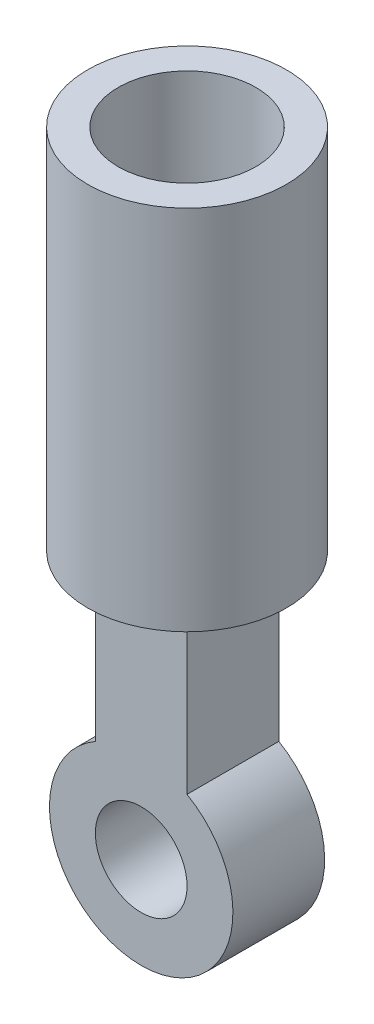
SolidWorks part; units mm, degrees
ref_plane "Front" through (0, 0, 0) normal (0, 0, 1) x (1, 0, 0)
ref_plane "Top" through (0, 0, 0) normal (0, 1, 0) x (1, 0, 0)
ref_plane "Right" through (0, 0, 0) normal (1, 0, 0) x (0, 0, -1)
sketch "Croquis1" plane through (0, 0, 0) normal (0, 0, 1) x (1, 0, 0)
  line L0 (0, 0) -> (0, 10) construction
  line L1 (1.5, 10) -> (-1.5, 10)
  line L2 (-1.5, 10) -> (-1.5, 2.5981)
  line L3 (1.5, 10) -> (1.5, 2.5981)
  circle A0 centre (0, 0) radius 1.5
  arc A1 (-1.5, 2.5981) -> (1.5, 2.5981) centre (0, 0) ccw
  dimension "D1" = 3
  dimension "D2" = 6
  dimension "D3" = 10
  dimension "D4" = 1.5
extrude "Saliente-Extruir1" add sketch "Croquis1" along normal blind 3
sketch "Croquis2" plane through (0, 10, 0) normal (0, 1, 0) x (1, 0, 0)
  line L0 (1.5, 0) -> (-1.5, -3) construction
  line L1 (-1.5, -3) -> (-1.5, 0) construction
  line L2 (-1.5, 0) -> (1.5, -3) construction
  circle A0 centre (0, -1.5) radius 3.25
  dimension "D1" = 6.5
extrude "Saliente-Extruir2" add sketch "Croquis2" along normal blind 10 and the other way blind 2
shell "Vaciado1" thickness 1 removed face at (0, 20, 4.75)
